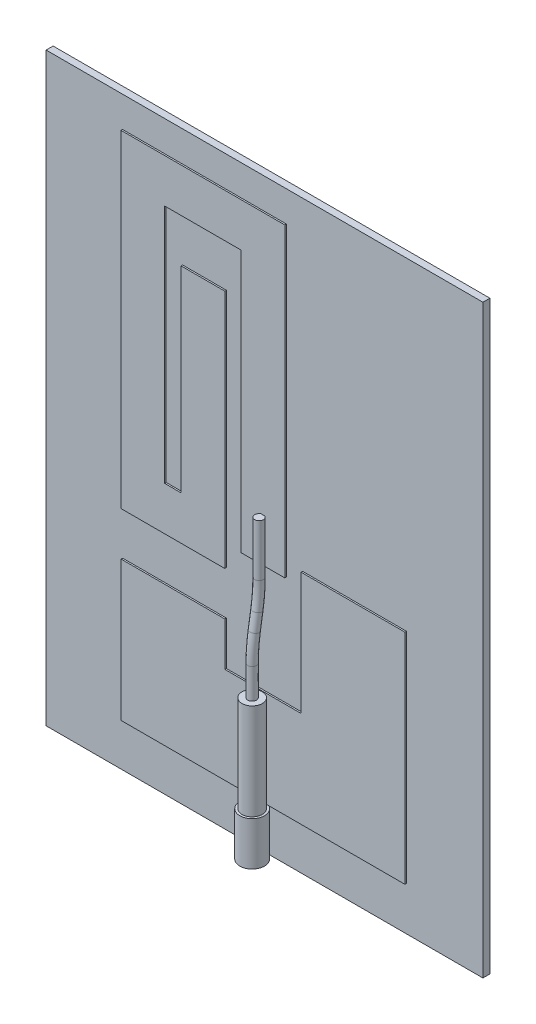
SolidWorks part; units mm, degrees
ref_plane "Front Plane" through (0, 0, 0) normal (0, 0, 1) x (1, 0, 0)
ref_plane "Top Plane" through (0, 0, 0) normal (0, 1, 0) x (1, 0, 0)
ref_plane "Right Plane" through (0, 0, 0) normal (1, 0, 0) x (0, 0, -1)
sketch "Sketch1" plane through (0, 0, 0) normal (0, 0, 1) x (1, 0, 0)
  line L1 (-10, -13.4) -> (10, -13.4)
  line L2 (-10, -13.4) -> (-10, 13.4)
  line L3 (-10, 13.4) -> (10, 13.4)
  line L4 (10, -13.4) -> (10, 13.4)
  point P4 (-10, 0)
  point P6 (0, -13.4)
  dimension "D1" = 20
  dimension "D2" = 26.8
extrude "Boss-Extrude1" add sketch "Sketch1" against normal blind 0.17
extrude "Boss-Extrude2" add sketch "Sketch1<2>" against normal blind 0.15 from surface starting at face at (0, 0, -0.17)
sketch "Sketch1<2>" plane through (0, 0, 0) normal (0, 0, 1) x (1, 0, 0) same geometry as "Sketch1"
sketch "Sketch2" plane through (0, 0, 0) normal (0, 0, 1) x (1, 0, 0)
  line L0 (0, -2) -> (0, 11) construction
  line L1 (0, 11) -> (-5.5, 11) construction
  line L2 (-5.5, 11) -> (-5.5, -2) construction
  line L3 (-5.5, -2) -> (-2.75, -2) construction
  line L4 (-2.75, -2) -> (-2.75, 8) construction
  line L5 (1, -2) -> (1, 12)
  line L6 (1, 12) -> (-6.5, 12)
  line L7 (-6.5, 12) -> (-6.5, -3)
  line L8 (-6.5, -3) -> (-1.75, -3)
  line L9 (-1.75, -3) -> (-1.75, 8)
  line L10 (-1, -2) -> (-1, 10)
  line L11 (-1, 10) -> (-4.5, 10)
  line L12 (-4.5, 10) -> (-4.5, -1)
  line L13 (-4.5, -1) -> (-3.75, -1)
  line L14 (-3.75, -1) -> (-3.75, 8)
  line L15 (1, -2) -> (-1, -2)
  line L16 (-1.75, 8) -> (-3.75, 8)
  line L17 (-6.5, -5) -> (-1.75, -5)
  line L18 (-1.75, -5) -> (-1.75, -7)
  line L19 (-1.75, -7) -> (1.75, -7)
  line L20 (1.75, -7) -> (1.75, -1.4)
  line L21 (1.75, -1.4) -> (6.5, -1.4)
  line L22 (6.5, -1.4) -> (6.5, -11.4)
  line L23 (6.5, -11.4) -> (-6.5, -11.4)
  line L24 (-6.5, -11.4) -> (-6.5, -5)
  line L25 (-10, -13.4) -> (10, -13.4) construction
  point P8 (-2.75, 11)
  point P29 (0, -7)
  dimension "D1" = 5.5
  dimension "D2" = 13
  dimension "D3" = 2
  dimension "D4" = 10
  dimension "D5" = 1
  dimension "D7" = 2
  dimension "D8" = 2
  dimension "D9" = 2
  dimension "D10" = 10
  dimension "D6" = 1
extrude "Boss-Extrude3" add sketch "Sketch2" along normal blind 0.07
sketch "Sketch3" plane through (0, -13.4, 0) normal (0, -1, 0) x (1, 0, 0)
  line L0 (-10, 0) -> (10, 0) construction
  circle A0 centre (0, 0.565) radius 0.565
  dimension "D1" = 1.13
extrude "Boss-Extrude8" add sketch "Sketch3" against normal blind 2 separate body contours A0 region at (0, -13.4, 0.565)
sketch "Sketch4" plane through (0, -11.4, 0) normal (0, 1, 0) x (1, 0, 0)
  circle A2 centre (0, -0.565) radius 0.465
  circle A3 centre (0, -0.565) radius 0.465
  dimension "D1" = 0.1
extrude "Boss-Extrude9" add sketch "Sketch4" along normal up to vertex (4.4 mm away) up to point (1.75, -7, 0)
sketch "Sketch5" plane through (0, 0, 0) normal (1, 0, 0) x (0, 0, -1)
  line L0 (-0.565, -7) -> (-0.565, -5.6261)
  line L1 (-0.1, -7) -> (-1.03, -7) construction
  line L2 (-0.4676, -4.3815) -> (-0.3474, -3.6185)
  line L3 (-0.25, -2.3739) -> (-0.25, 0)
  arc A0 (-0.3474, -3.6185) -> (-0.25, -2.3739) centre (-8.25, -2.3739) ccw
  arc A1 (-0.565, -5.6261) -> (-0.4676, -4.3815) centre (7.435, -5.6261) cw
  point P10 (-0.25, -3)
  point P13 (-0.565, -5)
  dimension "D4" = 8
  dimension "D1" = 0.25
  dimension "D2" = 3
  dimension "D3" = 2
sweep "Sweep4" add path "Sketch5" circular profile diameter 0.4 parameters "D3"=0.4
